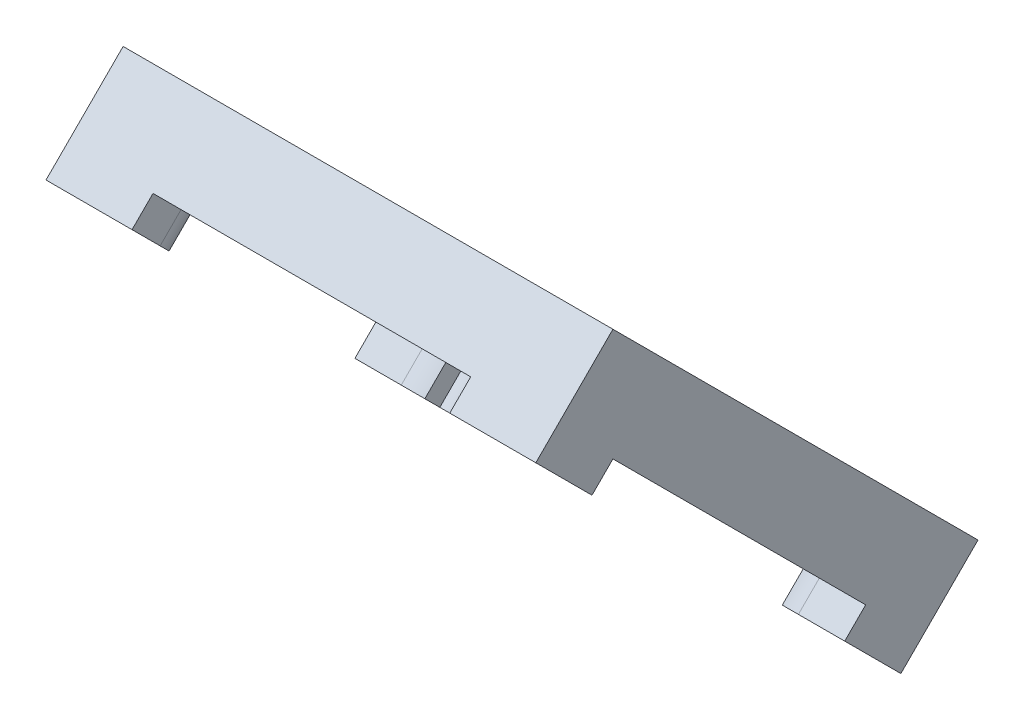
SolidWorks part; units mm, degrees
ref_plane "Front Plane" through (0, 0, 0) normal (0, 0, 1) x (1, 0, 0)
ref_plane "Top Plane" through (0, 0, 0) normal (0, 1, 0) x (1, 0, 0)
ref_plane "Right Plane" through (0, 0, 0) normal (1, 0, 0) x (0, 0, -1)
sketch "Sketch3" plane through (0, -51.2186, 51.2186) normal (0, -0.7071, 0.7071) x (1, 0, 0)
  line L0 (55.3446, 107.8122) -> (55.3446, 146.8122) construction
  line L1 (55.3446, 107.8122) -> (55.3446, 146.8122)
  line L2 (92.3446, 107.8122) -> (55.3446, 107.8122) construction
  line L3 (92.3446, 146.8122) -> (92.3446, 107.8122) construction
  line L4 (55.3446, 146.8122) -> (92.3446, 146.8122) construction
  line L5 (92.3446, 107.8122) -> (55.3446, 107.8122)
  line L6 (92.3446, 146.8122) -> (92.3446, 107.8122)
  line L7 (55.3446, 146.8122) -> (92.3446, 146.8122)
  circle A0 centre (73.8446, 131.3122) radius 12 construction
  circle A1 centre (73.8446, 131.3122) radius 12
extrude "Boss-Extrude1" add sketch "Sketch3" against normal up to surface (4.5 mm away)
sketch "Sketch4" plane through (0, -48.0366, 48.0366) normal (0, 0.7071, -0.7071) x (1, 0, 0)
  line L0 (92.3446, -146.8122) -> (92.3446, -107.8122) construction
  line L1 (55.3446, -146.8122) -> (92.3446, -146.8122) construction
  line L2 (55.3446, -107.8122) -> (55.3446, -146.8122) construction
  line L3 (92.3446, -107.8122) -> (55.3446, -107.8122) construction
  line L4 (92.3446, -146.8122) -> (92.3446, -107.8122)
  line L5 (55.3446, -146.8122) -> (92.3446, -146.8122)
  line L6 (55.3446, -107.8122) -> (55.3446, -146.8122)
  line L7 (92.3446, -107.8122) -> (55.3446, -107.8122)
  circle A0 centre (73.8446, -131.3122) radius 13 construction
  circle A1 centre (73.8446, -131.3122) radius 13
extrude "Boss-Extrude2" add sketch "Sketch4" along normal up to surface (1.5 mm away) up to face at (73.8446, 33.1479, 135.5851)
sketch "Sketch5" plane through (0, -51.2186, 51.2186) normal (0, -0.7071, 0.7071) x (1, 0, 0)
  line L0 (92.3446, 107.8122) -> (92.3446, 146.8122) construction
  line L1 (55.3446, 107.8122) -> (92.3446, 107.8122) construction
  line L2 (55.3446, 146.8122) -> (55.3446, 107.8122) construction
  line L3 (92.3446, 146.8122) -> (55.3446, 146.8122) construction
  line L4 (92.3446, 107.8122) -> (92.3446, 113.8122)
  line L5 (55.3446, 107.8122) -> (60.3446, 107.8122)
  line L6 (55.3446, 146.8122) -> (55.3446, 140.8122)
  line L7 (92.3446, 146.8122) -> (85.8446, 146.8122)
  line L8 (61.8446, 143.8122) -> (61.8446, 146.8122)
  line L9 (58.8446, 140.8122) -> (55.3446, 140.8122)
  line L10 (85.8446, 143.8122) -> (85.8446, 146.8122)
  line L11 (88.8446, 140.8122) -> (92.3446, 140.8122)
  line L12 (58.8446, 113.8122) -> (55.3446, 113.8122)
  line L13 (88.8446, 113.8122) -> (92.3446, 113.8122)
  line L14 (60.3446, 107.8122) -> (60.3446, 109.8122)
  line L15 (87.3446, 107.8122) -> (87.3446, 109.8122)
  line L16 (55.3446, 113.8122) -> (55.3446, 107.8122)
  line L17 (61.8446, 146.8122) -> (55.3446, 146.8122)
  line L18 (92.3446, 140.8122) -> (92.3446, 146.8122)
  line L19 (87.3446, 107.8122) -> (92.3446, 107.8122)
  line L20 (87.3446, 111.8073) -> (87.7222, 111.8073)
  line L21 (87.3446, 109.8122) -> (87.7266, 109.8122)
  line L22 (87.3446, 111.8073) -> (87.3446, 113.4103)
  line L23 (60.3446, 111.8122) -> (59.9626, 111.8122)
  line L24 (60.3446, 109.8122) -> (59.9626, 109.8122)
  line L25 (60.3446, 111.8122) -> (60.3446, 113.4103)
  circle A0 centre (88.8446, 110.8122) radius 1.5 construction
  circle A1 centre (88.8446, 143.8122) radius 1.5 construction
  circle A2 centre (58.8446, 143.8122) radius 1.5 construction
  circle A3 centre (58.8446, 110.8122) radius 1.5 construction
  arc A4 (87.7266, 109.8122) -> (87.7222, 111.8073) centre (88.8446, 110.8122) ccw
  circle A5 centre (88.8446, 143.8122) radius 1.5 construction
  circle A6 centre (58.8446, 143.8122) radius 1.5 construction
  arc A7 (59.9626, 111.8122) -> (59.9626, 109.8122) centre (58.8446, 110.8122) ccw
  arc A8 (85.8446, 143.8122) -> (88.8446, 140.8122) centre (88.8446, 143.8122) ccw
  arc A9 (58.8446, 140.8122) -> (61.8446, 143.8122) centre (58.8446, 143.8122) ccw
  arc A10 (60.3446, 113.4103) -> (58.8446, 113.8122) centre (58.8446, 110.8122) ccw
  arc A12 (88.8446, 113.8122) -> (87.3446, 113.4103) centre (88.8446, 110.8122) ccw
  circle A13 centre (58.8446, 110.8122) radius 1.5 construction
  circle A14 centre (88.8446, 143.8122) radius 1.25
  circle A15 centre (58.8446, 143.8122) radius 1.25
  dimension "D1" = 6
  dimension "D2" = 6
  dimension "D3" = 6
  dimension "D4" = 0.9951
  dimension "D10" = 2.5
  dimension "D11" = 2.5
  dimension "D5" = 5
  dimension "D6" = 5
  dimension "D7" = 1
  dimension "D8" = 1
  dimension "D9" = 1
extrude "Boss-Extrude4" add sketch "Sketch5" along normal offset from surface (2.2389 mm away) 1.5
ref_plane "Plane2" through (0, -46.0842, 46.0842) normal (0, 0.7071, -0.7071) x (1, 0, 0)
sketch "Sketch7" plane through (0, -46.0842, 46.0842) normal (0, 0.7071, -0.7071) x (1, 0, 0)
  line L0 (87.3446, -107.8122) -> (87.3446, -109.8122) construction
  line L1 (60.3446, -107.8122) -> (87.3446, -107.8122)
  line L2 (60.3446, -107.8122) -> (60.3446, -117.8122)
  line L3 (60.3446, -117.8122) -> (87.3446, -117.8122)
  line L4 (87.3446, -107.8122) -> (87.3446, -117.8122)
  dimension "D1" = 10
extrude "Cut-Extrude1" cut sketch "Sketch7" against normal up to surface (7.2611 mm away) and the other way blind 3 up to face at (73.8445, 35.0378, 137.475)
